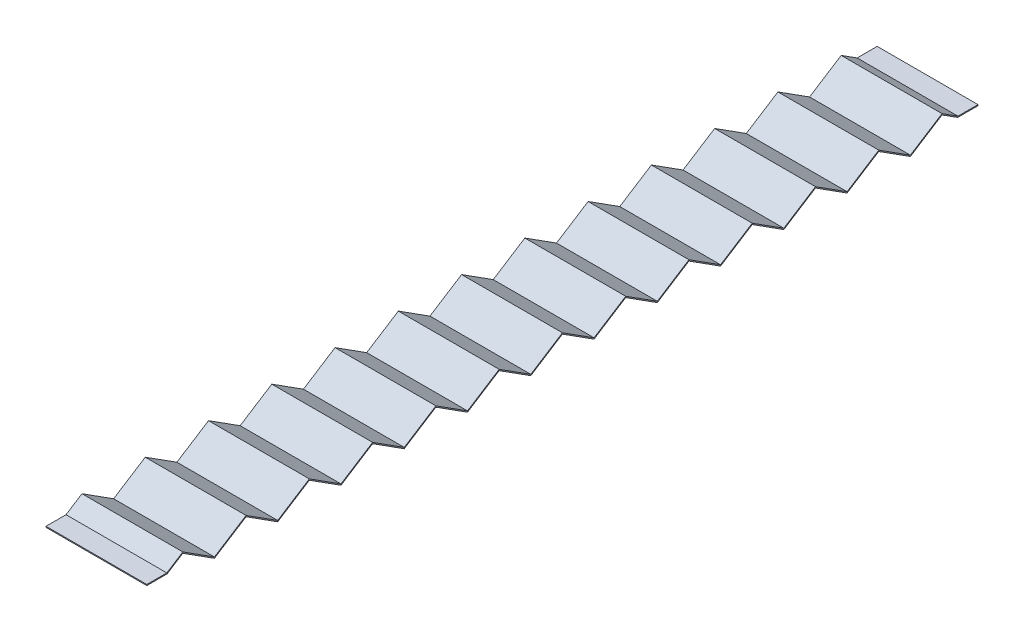
SolidWorks part; units mm, degrees
ref_plane "Front Plane" through (0, 0, 0) normal (0, 0, 1) x (1, 0, 0)
ref_plane "Top Plane" through (0, 0, 0) normal (0, 1, 0) x (1, 0, 0)
ref_plane "Right Plane" through (0, 0, 0) normal (1, 0, 0) x (0, 0, -1)
sketch "Sketch2" plane through (0, 0, 0) normal (0, 0, 1) x (1, 0, 0)
  line L1 (-27.5, 10) -> (27.5, 10)
  line L2 (-27.5, 10) -> (-27.5, 0)
  line L3 (-27.5, 0) -> (27.5, 0)
  line L4 (27.5, 10) -> (27.5, 0)
  point P4 (0, 0)
  dimension "D1" = 10
  dimension "D2" = 55
sketch "Sketch3" plane through (0, 0, 0) normal (1, 0, 0) x (0, 0, -1)
  line L0 (0, 10) -> (412.1793, 10) construction
  line L1 (0, 0) -> (412.1793, 0) construction
  line L3 (10, 5) -> (17.8436, 10)
  line L4 (17.8436, 10) -> (33.5308, 0)
  line L5 (33.5308, 0) -> (49.2179, 10)
  line L6 (49.2179, 10) -> (64.9051, 0)
  line L7 (64.9051, 0) -> (80.5923, 10)
  line L8 (80.5923, 10) -> (96.2794, 0)
  line L9 (96.2794, 0) -> (111.9666, 10)
  line L10 (111.9666, 10) -> (127.6538, 0)
  line L11 (127.6538, 0) -> (143.341, 10)
  line L12 (143.341, 10) -> (159.0281, 0)
  line L13 (159.0281, 0) -> (174.7153, 10)
  line L14 (174.7153, 10) -> (190.4025, 0)
  line L15 (190.4025, 0) -> (206.0897, 10)
  line L16 (206.0897, 10) -> (221.7768, 0)
  line L17 (221.7768, 0) -> (237.464, 10)
  line L18 (237.464, 10) -> (253.1512, 0)
  line L19 (0, 10) -> (0, 0) construction
  line L20 (253.1512, 0) -> (268.8383, 10)
  line L21 (268.8383, 10) -> (284.5255, 0)
  line L22 (284.5255, 0) -> (300.2127, 10)
  line L23 (300.2127, 10) -> (315.8999, 0)
  line L24 (315.8999, 0) -> (331.587, 10)
  line L25 (331.587, 10) -> (347.2742, 0)
  line L26 (347.2742, 0) -> (362.9614, 10)
  line L27 (362.9614, 10) -> (378.6485, 0)
  line L28 (378.6485, 0) -> (394.3357, 10)
  line L29 (394.3357, 10) -> (402.1793, 5)
  line L30 (412.1793, 10) -> (412.1793, 0) construction
  line L31 (10, 5) -> (0, 5)
  line L32 (402.1793, 5) -> (412.1793, 5)
  line L34 (412.1793, 22.75) -> (412.1793, 4.75) construction
  dimension "D2" = 10
  dimension "D1" = 10
  dimension "D3" = 10
extrude "Extrude-Thin1" add sketch "Sketch3" against normal mid plane 50 thin thin type mid plane wall 0.5
